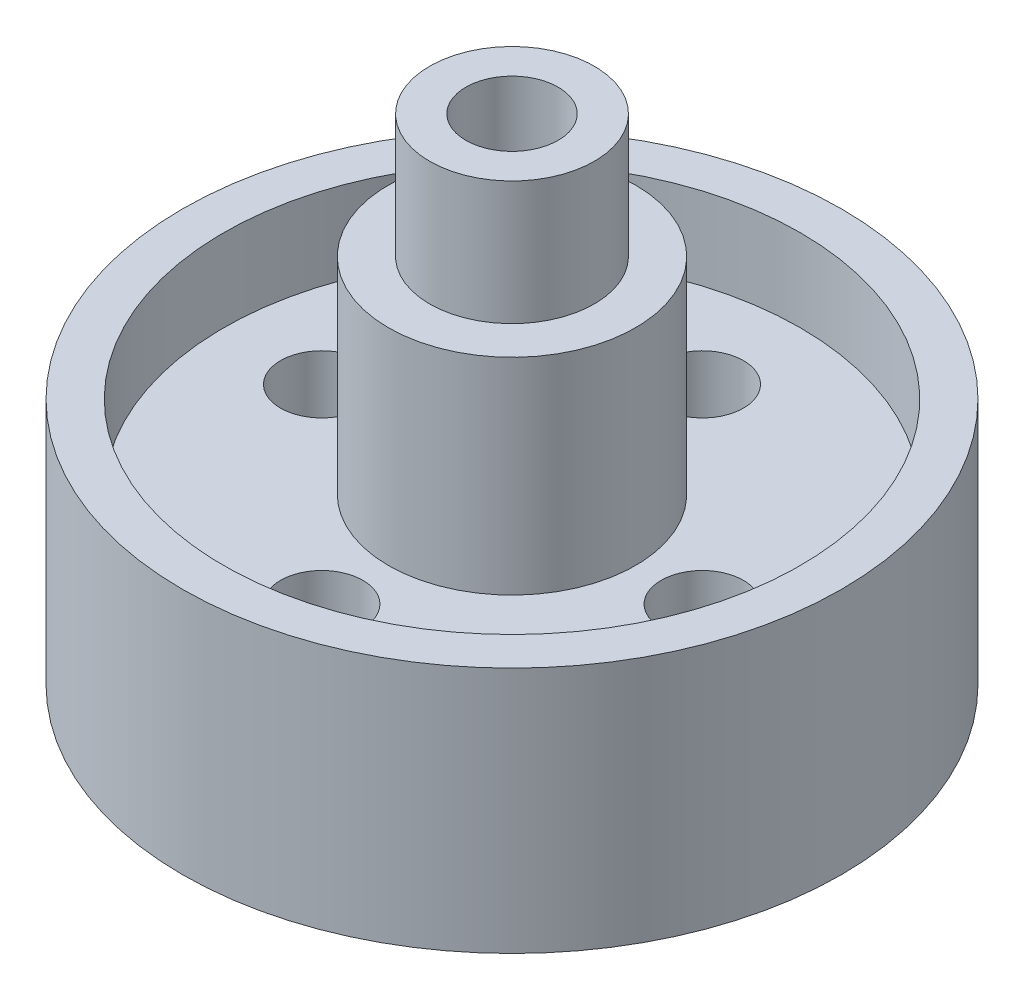
SolidWorks part; units mm, degrees
ref_plane "Front Plane" through (0, 0, 0) normal (0, 0, 1) x (1, 0, 0)
ref_plane "Top Plane" through (0, 0, 0) normal (0, 1, 0) x (1, 0, 0)
ref_plane "Right Plane" through (0, 0, 0) normal (1, 0, 0) x (0, 0, -1)
sketch "Sketch1" plane through (0, 0, 0) normal (0, 1, 0) x (1, 0, 0)
  circle A0 centre (0, 0) radius 50.8
  circle A1 centre (0, 0) radius 44.45
  circle A2 centre (0, 0) radius 19.05
  circle A3 centre (0, 0) radius 12.7
  circle A4 centre (0, 0) radius 7.112
extrude "Boss-Extrude1" add sketch "Sketch1" along normal blind 38.1 contours A0 A1 region at (-49.3632, 0, 0)
extrude "Boss-Extrude2" add sketch "Sketch1<3>" along normal blind 25.4 contours A1 A2 region at (-43.1928, 0, 0)
sketch "Sketch1<3>" plane through (0, 0, 0) normal (0, 1, 0) x (1, 0, 0) same geometry as "Sketch1"
extrude "Boss-Extrude3" add sketch "Sketch1<5>" along normal blind 57.15 contours A2 A3 region at (-18.5112, 0, 0)
sketch "Sketch1<5>" plane through (0, 0, 0) normal (0, 1, 0) x (1, 0, 0) same geometry as "Sketch1"
extrude "Boss-Extrude4" add sketch "Sketch1<6>" along normal blind 76.2 contours A3 A4 region at (-12.3408, 0, 0)
sketch "Sketch1<6>" plane through (0, 0, 0) normal (0, 1, 0) x (1, 0, 0) same geometry as "Sketch1"
sketch "Sketch2" plane through (0, 0, 0) normal (0, 1, 0) x (1, 0, 0)
  circle A0 centre (0, 0) radius 29.337 construction
  circle A1 centre (0, 29.337) radius 6.35
extrude "Cut-Extrude5" cut sketch "Sketch2" against normal blind 76.2 from surface contours A1 starting at face at (0, 25.4, 19.05)
pattern_circular "CirPattern1" count 4 over 360 about axis through (0, 25.4, 0) along (0, 1, 0) of "Cut-Extrude5"
